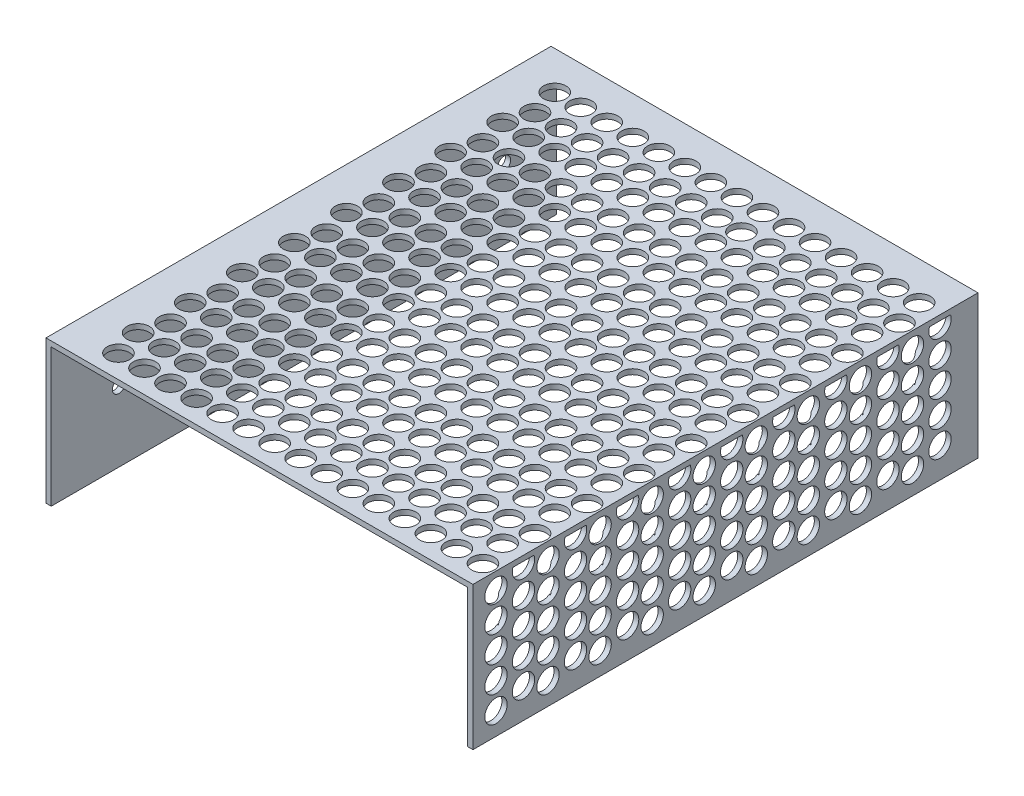
SolidWorks part; units mm, degrees
ref_plane "Спереди" through (0, 0, 0) normal (0, 0, 1) x (1, 0, 0)
ref_plane "Сверху" through (0, 0, 0) normal (0, 1, 0) x (1, 0, 0)
ref_plane "Справа" through (0, 0, 0) normal (1, 0, 0) x (0, 0, -1)
sketch "Эскиз1" plane through (0, 0, 0) normal (0, 0, 1) x (1, 0, 0)
  line L0 (81, 0) -> (81, 27.5)
  line L1 (81, 27.5) -> (1, 27.5)
  line L2 (1, 27.5) -> (1, 0)
  line L3 (0, 0) -> (1, 0)
  line L4 (82, 0) -> (82, 28.5)
  line L5 (82, 28.5) -> (0, 28.5)
  line L6 (0, 28.5) -> (0, 0)
  line L7 (81, 0) -> (82, 0)
  dimension "D1" = 1
  dimension "D2" = 1
  dimension "D3" = 1
  dimension "D4" = 80
extrude "Бобышка-Вытянуть1" add sketch "Эскиз1" along normal blind 99
sketch "Эскиз2" plane through (82, 0, 0) normal (1, 0, 0) x (0, 0, -1)
  line L0 (-98, 28.5) -> (-98, 1)
  line L1 (-99, 28.5) -> (0, 28.5) construction
  line L5 (-98, 1) -> (-1, 1)
  line L6 (0, 28.5) -> (-1, 28.5)
  line L7 (-1, 28.5) -> (-1, 1)
  line L9 (-98, 28.5) -> (-99, 28.5)
  line L10 (-99, 28.5) -> (-99, 0)
  line L12 (-99, 0) -> (0, 0)
  line L13 (0, 28.5) -> (0, 0)
  dimension "D1" = 1
  dimension "D2" = 1
extrude "Вырез-Вытянуть1" cut sketch "Эскиз2" against normal through all
sketch "Эскиз3" plane through (0, 28.5, 0) normal (0, 1, 0) x (1, 0, 0)
  line L0 (0, -98) -> (0, -1) construction
  line L1 (0, 0) -> (51.5, 0) construction
  circle A0 centre (8, -8.3) radius 2.15
  circle A1 centre (9.5, -13.582) radius 2.15
  circle A2 centre (13, -8.3) radius 2.15
  circle A3 centre (14.5, -13.582) radius 2.15
  circle A4 centre (18, -8.3) radius 2.15
  circle A5 centre (19.5, -13.582) radius 2.15
  circle A6 centre (23, -8.3) radius 2.15
  circle A7 centre (24.5, -13.582) radius 2.15
  circle A8 centre (28, -8.3) radius 2.15
  circle A9 centre (29.5, -13.582) radius 2.15
  circle A10 centre (33, -8.3) radius 2.15
  circle A11 centre (34.5, -13.582) radius 2.15
  circle A12 centre (38, -8.3) radius 2.15
  circle A13 centre (39.5, -13.582) radius 2.15
  circle A14 centre (43, -8.3) radius 2.15
  circle A15 centre (44.5, -13.582) radius 2.15
  circle A16 centre (48, -8.3) radius 2.15
  circle A18 centre (8, -18.3) radius 2.15
  circle A19 centre (9.5, -23.582) radius 2.15
  circle A20 centre (13, -18.3) radius 2.15
  circle A21 centre (14.5, -23.582) radius 2.15
  circle A22 centre (18, -18.3) radius 2.15
  circle A23 centre (19.5, -23.582) radius 2.15
  circle A24 centre (23, -18.3) radius 2.15
  circle A25 centre (24.5, -23.582) radius 2.15
  circle A26 centre (28, -18.3) radius 2.15
  circle A27 centre (29.5, -23.582) radius 2.15
  circle A28 centre (33, -18.3) radius 2.15
  circle A29 centre (34.5, -23.582) radius 2.15
  circle A30 centre (38, -18.3) radius 2.15
  circle A31 centre (39.5, -23.582) radius 2.15
  circle A32 centre (43, -18.3) radius 2.15
  circle A33 centre (44.5, -23.582) radius 2.15
  circle A34 centre (48, -18.3) radius 2.15
  circle A36 centre (8, -28.3) radius 2.15
  circle A37 centre (9.5, -33.582) radius 2.15
  circle A38 centre (13, -28.3) radius 2.15
  circle A39 centre (14.5, -33.582) radius 2.15
  circle A40 centre (18, -28.3) radius 2.15
  circle A41 centre (19.5, -33.582) radius 2.15
  circle A42 centre (23, -28.3) radius 2.15
  circle A43 centre (24.5, -33.582) radius 2.15
  circle A44 centre (28, -28.3) radius 2.15
  circle A45 centre (29.5, -33.582) radius 2.15
  circle A46 centre (33, -28.3) radius 2.15
  circle A47 centre (34.5, -33.582) radius 2.15
  circle A48 centre (38, -28.3) radius 2.15
  circle A49 centre (39.5, -33.582) radius 2.15
  circle A50 centre (43, -28.3) radius 2.15
  circle A51 centre (44.5, -33.582) radius 2.15
  circle A52 centre (48, -28.3) radius 2.15
  circle A54 centre (8, -38.3) radius 2.15
  circle A55 centre (9.5, -43.582) radius 2.15
  circle A56 centre (13, -38.3) radius 2.15
  circle A57 centre (14.5, -43.582) radius 2.15
  circle A58 centre (18, -38.3) radius 2.15
  circle A59 centre (19.5, -43.582) radius 2.15
  circle A60 centre (23, -38.3) radius 2.15
  circle A61 centre (24.5, -43.582) radius 2.15
  circle A62 centre (28, -38.3) radius 2.15
  circle A63 centre (29.5, -43.582) radius 2.15
  circle A64 centre (33, -38.3) radius 2.15
  circle A65 centre (34.5, -43.582) radius 2.15
  circle A66 centre (38, -38.3) radius 2.15
  circle A67 centre (39.5, -43.582) radius 2.15
  circle A68 centre (43, -38.3) radius 2.15
  circle A69 centre (44.5, -43.582) radius 2.15
  circle A70 centre (48, -38.3) radius 2.15
  circle A72 centre (8, -48.3) radius 2.15
  circle A73 centre (9.5, -53.582) radius 2.15
  circle A74 centre (13, -48.3) radius 2.15
  circle A75 centre (14.5, -53.582) radius 2.15
  circle A76 centre (18, -48.3) radius 2.15
  circle A77 centre (19.5, -53.582) radius 2.15
  circle A78 centre (23, -48.3) radius 2.15
  circle A79 centre (24.5, -53.582) radius 2.15
  circle A80 centre (28, -48.3) radius 2.15
  circle A81 centre (29.5, -53.582) radius 2.15
  circle A82 centre (33, -48.3) radius 2.15
  circle A83 centre (34.5, -53.582) radius 2.15
  circle A84 centre (38, -48.3) radius 2.15
  circle A85 centre (39.5, -53.582) radius 2.15
  circle A86 centre (43, -48.3) radius 2.15
  circle A87 centre (44.5, -53.582) radius 2.15
  circle A88 centre (48, -48.3) radius 2.15
  circle A90 centre (8, -58.3) radius 2.15
  circle A91 centre (9.5, -63.582) radius 2.15
  circle A92 centre (13, -58.3) radius 2.15
  circle A93 centre (14.5, -63.582) radius 2.15
  circle A94 centre (18, -58.3) radius 2.15
  circle A95 centre (19.5, -63.582) radius 2.15
  circle A96 centre (23, -58.3) radius 2.15
  circle A97 centre (24.5, -63.582) radius 2.15
  circle A98 centre (28, -58.3) radius 2.15
  circle A99 centre (29.5, -63.582) radius 2.15
  circle A100 centre (33, -58.3) radius 2.15
  circle A101 centre (34.5, -63.582) radius 2.15
  circle A102 centre (38, -58.3) radius 2.15
  circle A103 centre (39.5, -63.582) radius 2.15
  circle A104 centre (43, -58.3) radius 2.15
  circle A105 centre (44.5, -63.582) radius 2.15
  circle A106 centre (48, -58.3) radius 2.15
  circle A108 centre (8, -68.3) radius 2.15
  circle A109 centre (9.5, -73.582) radius 2.15
  circle A110 centre (13, -68.3) radius 2.15
  circle A111 centre (14.5, -73.582) radius 2.15
  circle A112 centre (18, -68.3) radius 2.15
  circle A113 centre (19.5, -73.582) radius 2.15
  circle A114 centre (23, -68.3) radius 2.15
  circle A115 centre (24.5, -73.582) radius 2.15
  circle A116 centre (28, -68.3) radius 2.15
  circle A117 centre (29.5, -73.582) radius 2.15
  circle A118 centre (33, -68.3) radius 2.15
  circle A119 centre (34.5, -73.582) radius 2.15
  circle A120 centre (38, -68.3) radius 2.15
  circle A121 centre (39.5, -73.582) radius 2.15
  circle A122 centre (43, -68.3) radius 2.15
  circle A123 centre (44.5, -73.582) radius 2.15
  circle A124 centre (48, -68.3) radius 2.15
  circle A127 centre (8, -78.3) radius 2.15
  circle A128 centre (9.5, -83.582) radius 2.15
  circle A129 centre (13, -78.3) radius 2.15
  circle A130 centre (14.5, -83.582) radius 2.15
  circle A131 centre (18, -78.3) radius 2.15
  circle A132 centre (19.5, -83.582) radius 2.15
  circle A133 centre (23, -78.3) radius 2.15
  circle A134 centre (24.5, -83.582) radius 2.15
  circle A135 centre (28, -78.3) radius 2.15
  circle A136 centre (29.5, -83.582) radius 2.15
  circle A137 centre (33, -78.3) radius 2.15
  circle A138 centre (34.5, -83.582) radius 2.15
  circle A139 centre (38, -78.3) radius 2.15
  circle A140 centre (39.5, -83.582) radius 2.15
  circle A141 centre (43, -78.3) radius 2.15
  circle A142 centre (44.5, -83.582) radius 2.15
  circle A143 centre (48, -78.3) radius 2.15
  circle A145 centre (8, -88.3) radius 2.15
  circle A146 centre (9.5, -93.582) radius 2.15
  circle A147 centre (13, -88.3) radius 2.15
  circle A148 centre (14.5, -93.582) radius 2.15
  circle A149 centre (18, -88.3) radius 2.15
  circle A150 centre (19.5, -93.582) radius 2.15
  circle A151 centre (23, -88.3) radius 2.15
  circle A152 centre (24.5, -93.582) radius 2.15
  circle A153 centre (28, -88.3) radius 2.15
  circle A154 centre (29.5, -93.582) radius 2.15
  circle A155 centre (33, -88.3) radius 2.15
  circle A156 centre (34.5, -93.582) radius 2.15
  circle A157 centre (38, -88.3) radius 2.15
  circle A158 centre (39.5, -93.582) radius 2.15
  circle A159 centre (43, -88.3) radius 2.15
  circle A160 centre (44.5, -93.582) radius 2.15
  circle A161 centre (48, -88.3) radius 2.15
  arc A163 (50.5, -11.6788) -> (50.5, -15.4853) centre (49.5, -13.582) ccw [skipped]
  circle A164 centre (53, -8.3) radius 2.15
  circle A165 centre (54.5, -13.582) radius 2.15
  circle A166 centre (58, -8.3) radius 2.15
  circle A167 centre (59.5, -13.582) radius 2.15
  circle A168 centre (63, -8.3) radius 2.15
  circle A169 centre (64.5, -13.582) radius 2.15
  circle A170 centre (68, -8.3) radius 2.15
  circle A171 centre (69.5, -13.582) radius 2.15
  circle A172 centre (73, -8.3) radius 2.15
  circle A173 centre (53, -18.3) radius 2.15
  circle A174 centre (54.5, -23.582) radius 2.15
  circle A175 centre (58, -18.3) radius 2.15
  circle A176 centre (59.5, -23.582) radius 2.15
  circle A177 centre (63, -18.3) radius 2.15
  circle A178 centre (64.5, -23.582) radius 2.15
  circle A179 centre (68, -18.3) radius 2.15
  circle A180 centre (69.5, -23.582) radius 2.15
  circle A181 centre (73, -18.3) radius 2.15
  circle A182 centre (53, -28.3) radius 2.15
  circle A183 centre (54.5, -33.582) radius 2.15
  circle A184 centre (58, -28.3) radius 2.15
  circle A185 centre (59.5, -33.582) radius 2.15
  circle A186 centre (63, -28.3) radius 2.15
  circle A187 centre (64.5, -33.582) radius 2.15
  circle A188 centre (68, -28.3) radius 2.15
  circle A189 centre (69.5, -33.582) radius 2.15
  circle A190 centre (73, -28.3) radius 2.15
  circle A191 centre (53, -38.3) radius 2.15
  circle A192 centre (54.5, -43.582) radius 2.15
  circle A193 centre (58, -38.3) radius 2.15
  circle A194 centre (59.5, -43.582) radius 2.15
  circle A195 centre (63, -38.3) radius 2.15
  circle A196 centre (64.5, -43.582) radius 2.15
  circle A197 centre (68, -38.3) radius 2.15
  circle A198 centre (69.5, -43.582) radius 2.15
  circle A199 centre (73, -38.3) radius 2.15
  circle A200 centre (53, -48.3) radius 2.15
  circle A201 centre (54.5, -53.582) radius 2.15
  circle A202 centre (58, -48.3) radius 2.15
  circle A203 centre (59.5, -53.582) radius 2.15
  circle A204 centre (63, -48.3) radius 2.15
  circle A205 centre (64.5, -53.582) radius 2.15
  circle A206 centre (68, -48.3) radius 2.15
  circle A207 centre (69.5, -53.582) radius 2.15
  circle A208 centre (73, -48.3) radius 2.15
  circle A209 centre (53, -58.3) radius 2.15
  circle A210 centre (54.5, -63.582) radius 2.15
  circle A211 centre (58, -58.3) radius 2.15
  circle A212 centre (59.5, -63.582) radius 2.15
  circle A213 centre (63, -58.3) radius 2.15
  circle A214 centre (64.5, -63.582) radius 2.15
  circle A215 centre (68, -58.3) radius 2.15
  circle A216 centre (69.5, -63.582) radius 2.15
  circle A217 centre (73, -58.3) radius 2.15
  circle A218 centre (53, -68.3) radius 2.15
  circle A219 centre (54.5, -73.582) radius 2.15
  circle A220 centre (58, -68.3) radius 2.15
  circle A221 centre (59.5, -73.582) radius 2.15
  circle A222 centre (63, -68.3) radius 2.15
  circle A223 centre (64.5, -73.582) radius 2.15
  circle A224 centre (68, -68.3) radius 2.15
  circle A225 centre (69.5, -73.582) radius 2.15
  circle A226 centre (73, -68.3) radius 2.15
  circle A227 centre (53, -78.3) radius 2.15
  circle A228 centre (54.5, -83.582) radius 2.15
  circle A229 centre (58, -78.3) radius 2.15
  circle A230 centre (59.5, -83.582) radius 2.15
  circle A231 centre (63, -78.3) radius 2.15
  circle A232 centre (64.5, -83.582) radius 2.15
  circle A233 centre (68, -78.3) radius 2.15
  circle A234 centre (69.5, -83.582) radius 2.15
  circle A235 centre (73, -78.3) radius 2.15
  circle A236 centre (53, -88.3) radius 2.15
  circle A237 centre (54.5, -93.582) radius 2.15
  circle A238 centre (58, -88.3) radius 2.15
  circle A239 centre (59.5, -93.582) radius 2.15
  circle A240 centre (63, -88.3) radius 2.15
  circle A241 centre (64.5, -93.582) radius 2.15
  circle A242 centre (68, -88.3) radius 2.15
  circle A243 centre (69.5, -93.582) radius 2.15
  circle A244 centre (73, -88.3) radius 2.15
  circle A245 centre (49.1513, -13.582) radius 2.15
  circle A246 centre (49.5, -93.582) radius 2.15
  circle A247 centre (49.5, -83.582) radius 2.15
  circle A248 centre (49.5, -73.582) radius 2.15
  circle A249 centre (49.5, -63.582) radius 2.15
  circle A250 centre (49.5, -53.582) radius 2.15
  circle A251 centre (49.5, -43.582) radius 2.15
  circle A252 centre (49.5, -33.582) radius 2.15
  circle A253 centre (49.5, -23.582) radius 2.15
  circle A254 centre (78, -8.3) radius 2.15
  circle A255 centre (79.5, -13.582) radius 2.15
  circle A260 centre (78, -18.3) radius 2.15
  circle A261 centre (79.5, -23.582) radius 2.15
  circle A266 centre (78, -28.3) radius 2.15
  circle A267 centre (79.5, -33.582) radius 2.15
  circle A272 centre (78, -38.3) radius 2.15
  circle A273 centre (79.5, -43.582) radius 2.15
  circle A278 centre (78, -48.3) radius 2.15
  circle A279 centre (79.5, -53.582) radius 2.15
  circle A284 centre (78, -58.3) radius 2.15
  circle A285 centre (79.5, -63.582) radius 2.15
  circle A290 centre (78, -68.3) radius 2.15
  circle A291 centre (79.5, -73.582) radius 2.15
  circle A296 centre (78, -78.3) radius 2.15
  circle A297 centre (79.5, -83.582) radius 2.15
  circle A302 centre (78, -88.3) radius 2.15
  circle A303 centre (79.5, -93.582) radius 2.15
  circle A308 centre (74.5, -13.582) radius 2.15
  circle A309 centre (74.5, -23.582) radius 2.15
  circle A310 centre (74.5, -33.582) radius 2.15
  circle A311 centre (74.5, -43.582) radius 2.15
  circle A312 centre (74.5, -53.582) radius 2.15
  circle A313 centre (74.5, -63.582) radius 2.15
  circle A314 centre (74.5, -73.582) radius 2.15
  circle A315 centre (74.5, -83.582) radius 2.15
  circle A316 centre (74.5, -93.582) radius 2.15
  dimension "D1" = 4.3
  dimension "D3" = 8.3
  dimension "D4" = 4.3
  dimension "D8" = 4.3
  dimension "D9" = 4.3
  dimension "D11" = 4.3
  dimension "D12" = 4.3
  dimension "D2" = 8
  dimension "D5" = 1.5
  dimension "D10" = 1.5
  dimension "D13" = 1.5
  dimension "D6" = 9
  dimension "D7" = 7
extrude "Вырез-Вытянуть2" cut sketch "Эскиз3" against normal blind 10
hole_wizard "Отверстие обработанное метчиком M31" positions "Эскиз4" profile "Эскиз5" tap size "M3" standard "ISO"
sketch "Эскиз4" plane through (0, 0, 0) normal (-1, 0, 0) x (0, 0, 1)
  line L2 (1, 28.5) -> (1, 1) construction
  line L3 (1, 1) -> (98, 1) construction
  point P0 (85, 14.5)
  point P2 (11, 14.5)
  dimension "D1" = 0
  dimension "D2" = 74
  dimension "D3" = 10
  dimension "D4" = 13.5
sketch "Эскиз5" plane through (0, 14.5, 85) normal (0, 1, 0) x (0, 0, 1)
  line L0 (0, 0) -> (0, 9.2511)
  line L1 (0, 9.2511) -> (1.25, 8.5)
  line L2 (1.25, 8.5) -> (1.25, 0)
  line L5 (1.25, 0) -> (0, 0)
  line L10 (0, 9.2511) -> (-1.25, 8.5) construction
  line L11 (0, -6.35) -> (0, 107.95) construction
  dimension "Диаметр сверла" = 2.5
  dimension "Глубина сверла" = 8.5
  dimension "Угол заточки сверла" = 118
cosmetic thread "Отверстие резьбы1" parameters "D1"=1, "D2"=3
cosmetic thread "Отверстие резьбы2" parameters "D1"=1, "D2"=3
sketch "Эскиз6" plane through (82, 0, 0) normal (1, 0, 0) x (0, 0, -1)
  line L16 (-60.3212, 27.5) -> (-56.2747, 27.5)
  line L18 (-70.3212, 27.5) -> (-66.2747, 27.5)
  line L19 (-50.3212, 27.5) -> (-46.2747, 27.5)
  line L20 (-40.3212, 27.5) -> (-36.2747, 27.5)
  line L21 (-30.3212, 27.5) -> (-26.2747, 27.5)
  line L22 (-20.3212, 27.5) -> (-16.2747, 27.5)
  line L23 (-10.3212, 27.5) -> (-6.2747, 27.5)
  line L24 (-90.3212, 27.5) -> (-86.2747, 27.5)
  line L25 (-80.3212, 27.5) -> (-76.2747, 27.5)
  circle A126 centre (-73.58, 5.2727) radius 2.15
  circle A127 centre (-68.298, 6.7727) radius 2.15
  circle A128 centre (-73.58, 10.2727) radius 2.15
  circle A129 centre (-68.298, 11.7727) radius 2.15
  circle A130 centre (-73.58, 15.2727) radius 2.15
  circle A131 centre (-68.298, 16.7727) radius 2.15
  circle A132 centre (-73.58, 20.2727) radius 2.15
  circle A133 centre (-68.298, 21.7727) radius 2.15
  circle A134 centre (-73.58, 25.2727) radius 2.15
  arc A135 (-70.3212, 27.5) -> (-66.2747, 27.5) centre (-68.298, 26.7727) ccw
  circle A144 centre (-63.58, 5.2727) radius 2.15
  circle A145 centre (-58.298, 6.7727) radius 2.15
  circle A146 centre (-63.58, 10.2727) radius 2.15
  circle A147 centre (-58.298, 11.7727) radius 2.15
  circle A148 centre (-63.58, 15.2727) radius 2.15
  circle A149 centre (-58.298, 16.7727) radius 2.15
  circle A150 centre (-63.58, 20.2727) radius 2.15
  circle A151 centre (-58.298, 21.7727) radius 2.15
  circle A152 centre (-63.58, 25.2727) radius 2.15
  arc A153 (-60.3212, 27.5) -> (-56.2747, 27.5) centre (-58.298, 26.7727) ccw
  circle A162 centre (-53.58, 5.2727) radius 2.15
  circle A163 centre (-48.298, 6.7727) radius 2.15
  circle A164 centre (-53.58, 10.2727) radius 2.15
  circle A165 centre (-48.298, 11.7727) radius 2.15
  circle A166 centre (-53.58, 15.2727) radius 2.15
  circle A167 centre (-48.298, 16.7727) radius 2.15
  circle A168 centre (-53.58, 20.2727) radius 2.15
  circle A169 centre (-48.298, 21.7727) radius 2.15
  circle A170 centre (-53.58, 25.2727) radius 2.15
  arc A171 (-50.3212, 27.5) -> (-46.2747, 27.5) centre (-48.298, 26.7727) ccw
  circle A180 centre (-43.58, 5.2727) radius 2.15
  circle A181 centre (-38.298, 6.7727) radius 2.15
  circle A182 centre (-43.58, 10.2727) radius 2.15
  circle A183 centre (-38.298, 11.7727) radius 2.15
  circle A184 centre (-43.58, 15.2727) radius 2.15
  circle A185 centre (-38.298, 16.7727) radius 2.15
  circle A186 centre (-43.58, 20.2727) radius 2.15
  circle A187 centre (-38.298, 21.7727) radius 2.15
  circle A188 centre (-43.58, 25.2727) radius 2.15
  arc A189 (-40.3212, 27.5) -> (-36.2747, 27.5) centre (-38.298, 26.7727) ccw
  circle A198 centre (-33.58, 5.2727) radius 2.15
  circle A199 centre (-28.298, 6.7727) radius 2.15
  circle A200 centre (-33.58, 10.2727) radius 2.15
  circle A201 centre (-28.298, 11.7727) radius 2.15
  circle A202 centre (-33.58, 15.2727) radius 2.15
  circle A203 centre (-28.298, 16.7727) radius 2.15
  circle A204 centre (-33.58, 20.2727) radius 2.15
  circle A205 centre (-28.298, 21.7727) radius 2.15
  circle A206 centre (-33.58, 25.2727) radius 2.15
  arc A207 (-30.3212, 27.5) -> (-26.2747, 27.5) centre (-28.298, 26.7727) ccw
  circle A216 centre (-23.58, 5.2727) radius 2.15
  circle A217 centre (-18.298, 6.7727) radius 2.15
  circle A218 centre (-23.58, 10.2727) radius 2.15
  circle A219 centre (-18.298, 11.7727) radius 2.15
  circle A220 centre (-23.58, 15.2727) radius 2.15
  circle A221 centre (-18.298, 16.7727) radius 2.15
  circle A222 centre (-23.58, 20.2727) radius 2.15
  circle A223 centre (-18.298, 21.7727) radius 2.15
  circle A224 centre (-23.58, 25.2727) radius 2.15
  arc A225 (-20.3212, 27.5) -> (-16.2747, 27.5) centre (-18.298, 26.7727) ccw
  circle A234 centre (-13.58, 5.2727) radius 2.15
  circle A235 centre (-8.298, 6.7727) radius 2.15
  circle A236 centre (-13.58, 10.2727) radius 2.15
  circle A237 centre (-8.298, 11.7727) radius 2.15
  circle A238 centre (-13.58, 15.2727) radius 2.15
  circle A239 centre (-8.298, 16.7727) radius 2.15
  circle A240 centre (-13.58, 20.2727) radius 2.15
  circle A241 centre (-8.298, 21.7727) radius 2.15
  circle A242 centre (-13.58, 25.2727) radius 2.15
  arc A243 (-10.3212, 27.5) -> (-6.2747, 27.5) centre (-8.298, 26.7727) ccw
  circle A259 centre (-93.58, 5.2727) radius 2.15
  circle A260 centre (-88.298, 6.7727) radius 2.15
  circle A261 centre (-93.58, 10.2727) radius 2.15
  circle A262 centre (-88.298, 11.7727) radius 2.15
  circle A263 centre (-93.58, 15.2727) radius 2.15
  circle A264 centre (-88.298, 16.7727) radius 2.15
  circle A265 centre (-93.58, 20.2727) radius 2.15
  circle A266 centre (-88.298, 21.7727) radius 2.15
  circle A267 centre (-93.58, 25.2727) radius 2.15
  arc A268 (-90.3212, 27.5) -> (-86.2747, 27.5) centre (-88.298, 26.7727) ccw
  circle A269 centre (-83.58, 5.2727) radius 2.15
  circle A270 centre (-78.298, 6.7727) radius 2.15
  circle A271 centre (-83.58, 10.2727) radius 2.15
  circle A272 centre (-78.298, 11.7727) radius 2.15
  circle A273 centre (-83.58, 15.2727) radius 2.15
  circle A274 centre (-78.298, 16.7727) radius 2.15
  circle A275 centre (-83.58, 20.2727) radius 2.15
  circle A276 centre (-78.298, 21.7727) radius 2.15
  circle A277 centre (-83.58, 25.2727) radius 2.15
  arc A278 (-80.3212, 27.5) -> (-76.2747, 27.5) centre (-78.298, 26.7727) ccw
extrude "Вырез-Вытянуть3" cut sketch "Эскиз6" against normal blind 24
